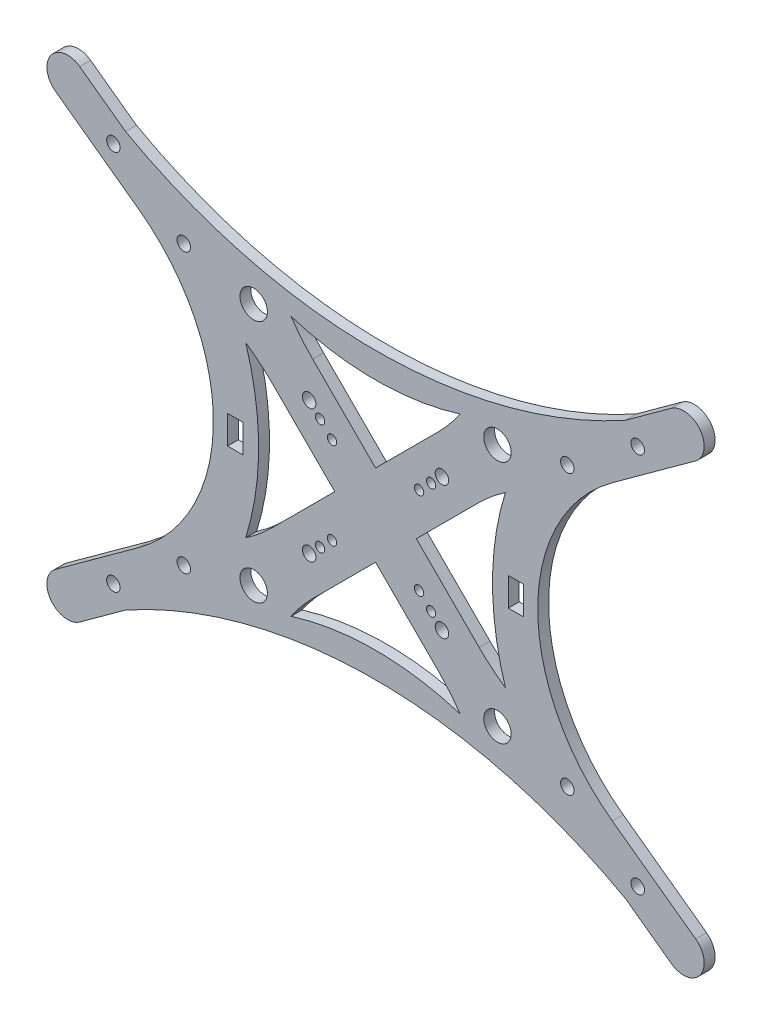
SolidWorks part; units mm, degrees
material "PPS"
ref_plane "前视基准面" through (0, 0, 0) normal (0, 0, 1) x (1, 0, 0)
ref_plane "上视基准面" through (0, 0, 0) normal (0, 1, 0) x (1, 0, 0)
ref_plane "右视基准面" through (0, 0, 0) normal (1, 0, 0) x (0, 0, -1)
sketch "草图7" plane through (0, 0, 0) normal (0, 0, 1) x (1, 0, 0)
  line L0 (-137.4469, 0) -> (193.7386, 0) construction
  line L1 (0, 90.5001) -> (0, -188.7446) construction
  line L2 (0, 0) -> (86.3378, -62.728) construction
  line L61 (-67.9485, -55.2388) -> (-57.4206, -47.5898)
  line L62 (-73.5325, -47.5531) -> (-54.395, -33.649)
  line L66 (-67.9485, 55.2388) -> (-57.4206, 47.5898)
  line L82 (-73.5325, 47.5531) -> (-54.395, 33.649)
  line L93 (73.5325, 47.5531) -> (54.395, 33.649)
  line L94 (-34, -3.25) -> (-34, 3.25) construction
  line L95 (67.9485, 55.2388) -> (57.4206, 47.5898)
  line L104 (15.25, 15.25) -> (0, 0) construction
  line L105 (67.9485, -55.2388) -> (57.4206, -47.5898)
  line L106 (73.5325, -47.5531) -> (54.395, -33.649)
  line L107 (0, 0) -> (86.3378, 62.728) construction
  circle A40 centre (10, 10) radius 1.075
  circle A65 centre (12.75, 12.75) radius 1.075
  circle A66 centre (15.25, 15.25) radius 1.55
  circle A73 centre (15.25, -15.25) radius 1.55
  circle A74 centre (12.75, -12.75) radius 1.075
  circle A75 centre (10, -10) radius 1.075
  circle A76 centre (28, -28) radius 3.15
  circle A89 centre (28, 28) radius 3.15
  arc A132 (67.9485, 55.2388) -> (73.5325, 47.5531) centre (70.7405, 51.396) cw
  arc A133 (54.395, 33.649) -> (54.395, -33.649) centre (78.8424, 0) ccw
  circle A134 centre (60.2246, 43.7557) radius 1.55
  arc A135 (-57.4206, -47.5898) -> (57.4206, -47.5898) centre (0, -151.3241) cw
  circle A136 centre (-60.2246, 43.7557) radius 1.55
  arc A138 (-54.395, 33.649) -> (-54.395, -33.649) centre (-78.8424, 0) cw
  arc A139 (-67.9485, 55.2388) -> (-73.5325, 47.5531) centre (-70.7405, 51.396) ccw
  circle A152 centre (-28, 28) radius 3.15
  circle A153 centre (-28, -28) radius 3.15
  circle A154 centre (-10, -10) radius 1.075
  circle A155 centre (-12.75, -12.75) radius 1.075
  circle A156 centre (-15.25, -15.25) radius 1.55
  circle A157 centre (-15.25, 15.25) radius 1.55
  circle A158 centre (-12.75, 12.75) radius 1.075
  circle A159 centre (-10, 10) radius 1.075
  arc A166 (-57.4206, 47.5898) -> (57.4206, 47.5898) centre (0, 151.3241) ccw
  arc A167 (67.9485, -55.2388) -> (73.5325, -47.5531) centre (70.7405, -51.396) ccw
  arc A172 (-67.9485, -55.2388) -> (-73.5325, -47.5531) centre (-70.7405, -51.396) cw
  circle A176 centre (60.2246, -43.7557) radius 1.55
  circle A177 centre (44.0442, -32) radius 1.55
  circle A178 centre (44.0442, 32) radius 1.55
  circle A179 centre (-44.0442, 32) radius 1.55
  circle A180 centre (-60.2246, -43.7557) radius 1.55
  circle A181 centre (-44.0442, -32) radius 1.55
  point P49 (-37.25, 0)
  dimension "D2" = 2.75
  dimension "D4" = 2.5
  dimension "D1" = 2.15
  dimension "D3" = 3.1
  dimension "D6" = 3.1
  dimension "D10" = 10
  dimension "D5" = 45
  dimension "D7" = 4.75
  dimension "D8" = 3.25
  dimension "D9" = 10
  dimension "D11" = 12.75
  dimension "D16" = 36
sketch "草图8" plane through (0, 0, 0) normal (0, 0, 1) x (1, 0, 0)
  line L0 (-96.7808, 0) -> (86.8563, 0) construction
  line L1 (0, 52.226) -> (0, -62.4511) construction
  line L2 (34, -3.25) -> (30.5, -3.25)
  line L3 (-34, 3.25) -> (-30.5, 3.25)
  line L4 (-34, 3.25) -> (-34, -3.25)
  line L5 (-34, -3.25) -> (-30.5, -3.25)
  line L6 (-30.5, 3.25) -> (-30.5, -3.25)
  line L7 (30.5, 3.25) -> (30.5, -3.25)
  line L8 (34, 3.25) -> (30.5, 3.25)
  line L9 (34, 3.25) -> (34, -3.25)
  dimension "D1" = 30.5
  dimension "D2" = 6.5
  dimension "D3" = 3.5
sketch "草图6" plane through (0, 0, 0) normal (0, 0, 1) x (1, 0, 0)
  line L3 (-23.8014, 14.4296) -> (-9.3719, 0)
  line L9 (-58.8867, 0) -> (57.6096, 0) construction
  line L14 (-23.8014, -14.4296) -> (-9.3719, 0)
  line L15 (0, 29.8455) -> (0, -115.5328) construction
  line L29 (14.4296, 23.8014) -> (0, 9.3719)
  line L30 (-14.4296, 23.8014) -> (0, 9.3719)
  line L31 (23.8014, -14.4296) -> (9.3719, 0)
  line L32 (23.8014, 14.4296) -> (9.3719, 0)
  line L33 (-14.4296, -23.8014) -> (0, -9.3719)
  line L34 (14.4296, -23.8014) -> (0, -9.3719)
  arc A18 (-23.8014, 14.4296) -> (-29.8202, 19.4008) centre (-52.8883, -14.6573) ccw
  arc A19 (-23.8014, -14.4296) -> (-29.8202, -19.4008) centre (-52.8883, 14.6573) cw
  arc A20 (-29.8202, -19.4008) -> (-29.8202, 19.4008) centre (-91.9966, 0) ccw
  arc A33 (-14.4296, 23.8014) -> (-19.4008, 29.8202) centre (14.6573, 52.8883) cw
  arc A34 (-19.4008, 29.8202) -> (19.4008, 29.8202) centre (0, 91.9966) ccw
  arc A35 (14.4296, 23.8014) -> (19.4008, 29.8202) centre (-14.6573, 52.8883) ccw
  arc A36 (23.8014, 14.4296) -> (29.8202, 19.4008) centre (52.8883, -14.6573) cw
  arc A37 (29.8202, 19.4008) -> (29.8202, -19.4008) centre (91.9966, 0) ccw
  arc A38 (23.8014, -14.4296) -> (29.8202, -19.4008) centre (52.8883, 14.6573) ccw
  arc A39 (14.4296, -23.8014) -> (19.4008, -29.8202) centre (-14.6573, -52.8883) cw
  arc A40 (19.4008, -29.8202) -> (-19.4008, -29.8202) centre (0, -91.9966) ccw
  arc A41 (-14.4296, -23.8014) -> (-19.4008, -29.8202) centre (14.6573, -52.8883) ccw
  point P49 (0, 0)
  dimension "D1" = 4
extrude "主结构-厚度还是得2.5, 不然铝柱不好选" add sketch "草图7" along normal blind 2.5
extrude "切除-拉伸2" cut sketch "草图6" along normal through all
extrude "切除-拉伸3" cut sketch "草图8" along normal through all
